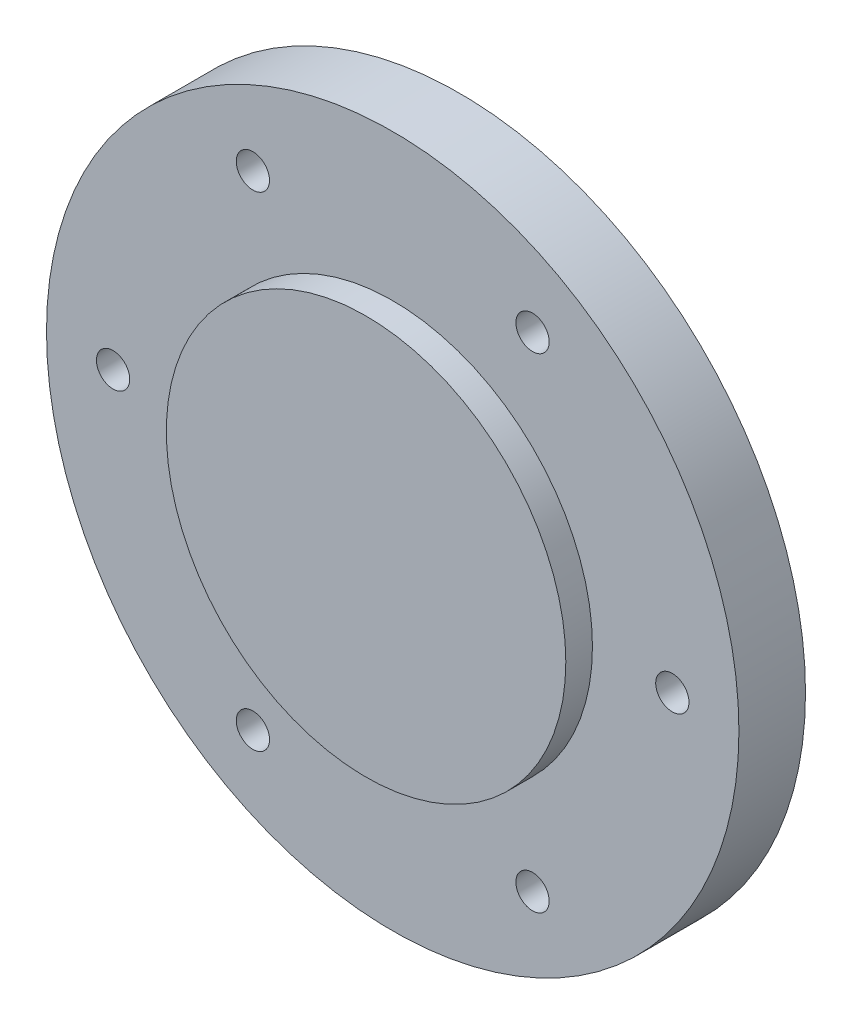
SolidWorks part; units mm, degrees
ref_plane "Front Plane" through (0, 0, 0) normal (0, 0, 1) x (1, 0, 0)
ref_plane "Top Plane" through (0, 0, 0) normal (0, 1, 0) x (1, 0, 0)
ref_plane "Right Plane" through (0, 0, 0) normal (1, 0, 0) x (0, 0, -1)
sketch "SK_Disc" plane through (0, 0, 0) normal (0, 0, 1) x (1, 0, 0)
  circle A0 centre (0, 0) radius 26
  dimension "D_disc" = 52
extrude "Output_Disc" add sketch "SK_Disc" along normal blind 5
ref_plane "PL_Mount" through (0, 0, 5) normal (0, 0, 1) x (1, 0, 0)
sketch "SK_Pilot" plane through (0, 0, 5) normal (0, 0, 1) x (1, 0, 0)
  circle A0 centre (0, 0) radius 15
  dimension "D_pil" = 30
extrude "Pilot_Boss" add sketch "SK_Pilot" along normal blind 2
sketch "SK_OutHole" plane through (0, 0, 5) normal (0, 0, 1) x (1, 0, 0)
  circle A0 centre (21, 0) radius 1.25
  dimension "D_oh" = 2.5
  dimension "R_oh" = 21
extrude "Output_Tapped_Hole" cut sketch "SK_OutHole" against normal blind 5
ref_axis "AX_Joint" through (0, 0, -0.35) along (0, 0, 1)
pattern_circular "Output_Hole_Pattern" count 6 over 360 about axis through (0, 0, -0.35) along (0, 0, 1) of "Output_Tapped_Hole"
equation "\"D_out\" = 52"
equation "\"T_out\" = 5"
equation "\"PCD_out\" = 42"
equation "\"D_pilot\" = 30"
equation "\"H_pilot\" = 2"
equation "\"D_out_hole\" = 2.5"
equation "\"D_disc@SK_Disc\" = \"D_out\""
equation "\"D1@Output_Disc\" = \"T_out\""
equation "\"D_pil@SK_Pilot\" = \"D_pilot\""
equation "\"D1@Pilot_Boss\" = \"H_pilot\""
equation "\"D_oh@SK_OutHole\" = \"D_out_hole\""
equation "\"R_oh@SK_OutHole\" = \"PCD_out\"/2"
